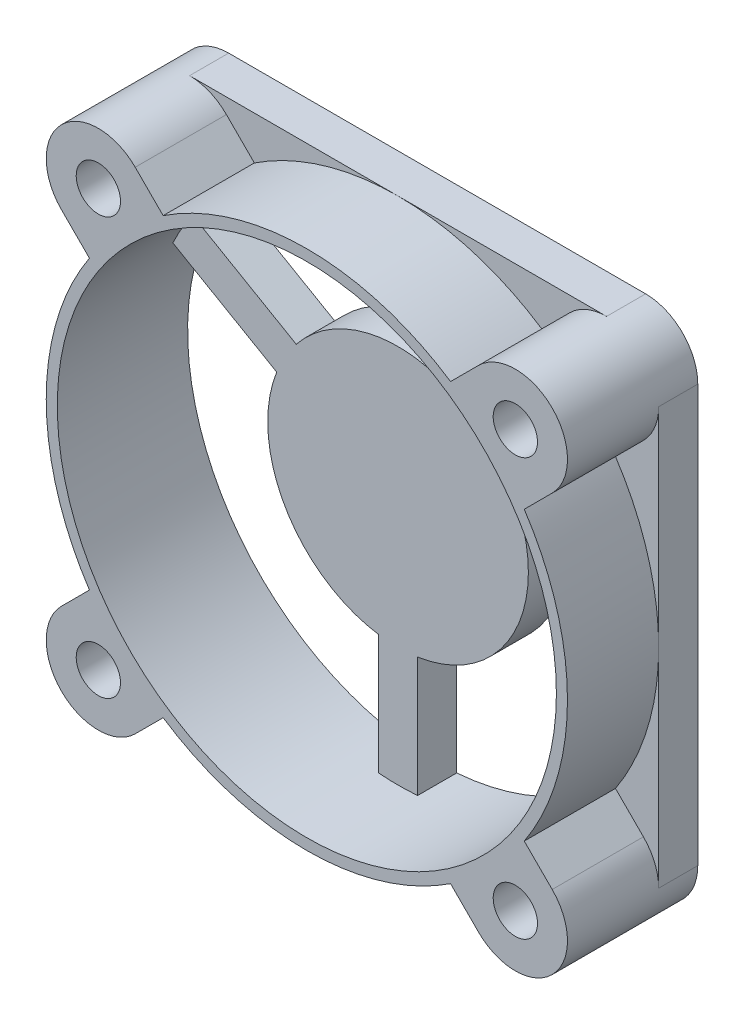
SolidWorks part; units mm, degrees
note: '?' marks a value the reader was unsure of.
material "PW100:Mi:0:30:C1:0:1:2:Re:16:"
ref_plane "Front" through (0, 0, 0) normal (0, 0, 1) x (1, 0, 0)
ref_plane "Top" through (0, 0, 0) normal (0, 1, 0) x (1, 0, 0)
ref_plane "Right" through (0, 0, 0) normal (1, 0, 0) x (0, 0, -1)
sketch "Support-Front" plane through (0, 0, 0) normal (0, 0, 1) x (1, 0, 0)
  line L0 (-20, 0) -> (20, 0) construction
  line L1 (0, 20) -> (0, -20) construction
  line L2 (20, -16) -> (20, 16)
  line L3 (-20, -16) -> (-20, 16)
  line L4 (16, 20) -> (-16, 20)
  line L5 (16, -20) -> (-16, -20)
  line L6 (0, 20) -> (0, 26.6274) construction
  arc A0 (20, 16) -> (16, 20) centre (16, 16) ccw
  arc A1 (-20, 16) -> (-16, 20) centre (-16, 16) cw
  arc A2 (-20, -16) -> (-16, -20) centre (-16, -16) ccw
  arc A3 (20, -16) -> (16, -20) centre (16, -16) cw
  circle A4 centre (16, 16) radius 1.7
  circle A5 centre (-16, 16) radius 1.7
  circle A6 centre (-16, -16) radius 1.7
  circle A7 centre (16, -16) radius 1.7
  circle A8 centre (0, 0) radius 19.15
  circle A9 centre (0, 0) radius 10
  circle A10 centre (0, 0) radius 20
  circle A11 centre (0, 0) radius 26.6274 construction
  dimension "Diam-Fixing-Hole" = 3.4
  dimension "Diam-Fan-Hole" = 38.3
  dimension "Diam-Fixing-Plate-Fan" = 20
  dimension "Width" = 40
  dimension "Dist-Fixing-Hole" = 32
sketch "Support-Right" plane through (0, 0, 0) normal (1, 0, 0) x (0, 0, -1)
  line L0 (-10, 0) -> (0, 0) construction
  line L1 (-5, 20) -> (-5, -20) construction
  line L2 (-3, 20) -> (-3, -20)
  line L3 (-10, 20) -> (0, 20)
  line L4 (-10, 20) -> (-10, -20)
  line L5 (-10, -20) -> (0, -20)
  line L6 (0, 20) -> (0, -20)
  line L7 (-7, 20) -> (-7, -20)
  dimension "Thickness" = 10
  dimension "Thickness-Flange" = 3
sketch "Support-Front-Reinforcment-Place" plane through (0, 0, 0) normal (0, 0, 1) x (1, 0, 0)
  line L0 (0, 20) -> (0, 0) construction
  line L2 (6.306, 20) -> (6.6671, 17.9519)
  line L3 (16, 20) -> (-16, 20) construction
  line L4 (-6.306, 20) -> (-6.6671, 17.9519)
  line L5 (6.306, 20) -> (0, 0) construction
  line L6 (-6.306, 20) -> (0, 0) construction
  line L7 (6.306, 20) -> (-6.306, 20)
  circle A3 centre (0, 0) radius 19.15 construction
  arc A4 (6.6671, 17.9519) -> (-6.6671, 17.9519) centre (0, 0) ccw
  dimension "D1" = 20
  dimension "D2" = 35
sketch "Support-Front-Reinforcment-Strip" plane through (0, 0, 0) normal (0, 0, 1) x (1, 0, 0)
  line L0 (11.028, 16.6848) -> (13.1716, 18.8284)
  line L1 (16.6848, 11.028) -> (18.8284, 13.1716)
  line L2 (16, 16) -> (0, 0) construction
  arc A0 (13.1716, 18.8284) -> (18.8284, 13.1716) centre (16, 16) cw
  arc A1 (20, 16) -> (16, 20) centre (16, 16) ccw construction
  circle A3 centre (0, 0) radius 20 construction
  arc A6 (16.6848, 11.028) -> (11.028, 16.6848) centre (0, 0) ccw
sketch "Support-Front-Bone" plane through (0, 0, 0) normal (0, 0, 1) x (1, 0, 0)
  line L0 (0, -10) -> (0, -19.15) construction
  line L1 (-1.5, -9.8869) -> (-1.5, -19.0912)
  line L2 (1.5, -9.8869) -> (1.5, -19.0912)
  line L3 (0, 0) -> (0, 20) construction
  line L4 (16, 20) -> (-16, 20) construction
  line L6 (0, 0) -> (0, -10) construction
  circle A0 centre (0, 0) radius 19.15 construction
  circle A1 centre (0, 0) radius 10 construction
  arc A2 (-1.5, -9.8869) -> (1.5, -9.8869) centre (0, 0) ccw
  arc A3 (-1.5, -19.0912) -> (1.5, -19.0912) centre (0, 0) ccw
  dimension "Angle-Bone" = 180
  dimension "Angle-Place-Bone" = 180
  dimension "Thickness-Flange" = 3
ref_plane "Plane1" through (0, 0, 10) normal (0, 0, 1) x (1, 0, 0)
sketch "Sketch-Body" plane through (0, 0, 0) normal (0, 0, 1) x (1, 0, 0)
  line L4 (-16, -20) -> (16, -20)
  line L5 (-20, 16) -> (-20, -16)
  line L6 (16, 20) -> (-16, 20)
  line L7 (20, -16) -> (20, 16)
  line L8 (-16, -20) -> (16, -20)
  line L9 (-20, 16) -> (-20, -16)
  line L10 (16, 20) -> (-16, 20)
  line L11 (20, -16) -> (20, 16)
  circle A0 centre (0, 0) radius 19.15 construction
  circle A1 centre (0, 0) radius 19.15
  arc A4 (-20, -16) -> (-16, -20) centre (-16, -16) ccw
  arc A5 (-16, 20) -> (-20, 16) centre (-16, 16) ccw
  arc A6 (20, 16) -> (16, 20) centre (16, 16) ccw
  arc A7 (16, -20) -> (20, -16) centre (16, -16) ccw
  arc A8 (-20, -16) -> (-16, -20) centre (-16, -16) ccw
  arc A9 (-16, 20) -> (-20, 16) centre (-16, 16) ccw
  arc A10 (20, 16) -> (16, 20) centre (16, 16) ccw
  arc A11 (16, -20) -> (20, -16) centre (16, -16) ccw
  dimension "D1" = 0
extrude "Body" add sketch "Sketch-Body" along normal up to surface (10 mm away) up to plane "Plane1"
sketch "Sketch-Cut-Body" plane through (0, 0, 0) normal (1, 0, 0) x (0, 0, -1)
  line L0 (-10, 0) -> (0, 0) construction
  line L1 (-10, 0) -> (0, 0) construction
  line L2 (-10, 19.15) -> (-10, -19.15) construction
  line L4 (-10, 20) -> (0, 20) construction
  line L5 (-10, 20) -> (-10, 26.6274)
  line L6 (-10, 26.6274) -> (-3, 26.6274)
  line L7 (-10, 20) -> (-3, 20)
  line L9 (-3, 26.6274) -> (-3, 20)
  line L10 (-3, 20) -> (-3, -20) construction
revolve "Cut-Body" cut sketch "Sketch-Cut-Body" angle 360 about L1
sketch "Sketch-Reinforcment-Place" plane through (0, 0, 0) normal (0, 0, 1) x (1, 0, 0)
  line L0 (16, 20) -> (-16, 20) construction
  line L1 (6.306, 20) -> (6.6671, 17.9519) construction
  line L2 (-6.306, 20) -> (-6.6671, 17.9519) construction
  line L3 (6.306, 20) -> (-6.306, 20)
  line L4 (6.306, 20) -> (6.6671, 17.9519)
  line L5 (-6.306, 20) -> (-6.6671, 17.9519)
  circle A0 centre (0, 0) radius 19.15 construction
  arc A1 (6.6671, 17.9519) -> (-6.6671, 17.9519) centre (0, 0) ccw
extrude "Reinforcment-Place" [suppressed] add sketch "Sketch-Reinforcment-Place" along normal up to surface (25.5 mm away)
pattern_circular "CirPattern-Reinforcment-Place" [suppressed] count 1 over? 360?
sketch "Sketch-Reinforcment-Strip" plane through (0, 0, 0) normal (0, 0, 1) x (1, 0, 0)
  line L0 (16.6848, 11.028) -> (18.8284, 13.1716) construction
  line L1 (11.028, 16.6848) -> (13.1716, 18.8284) construction
  line L2 (16.6848, 11.028) -> (18.8284, 13.1716)
  line L3 (11.028, 16.6848) -> (13.1716, 18.8284)
  arc A0 (18.8284, 13.1716) -> (13.1716, 18.8284) centre (16, 16) ccw construction
  circle A1 centre (0, 0) radius 20 construction
  arc A2 (18.8284, 13.1716) -> (13.1716, 18.8284) centre (16, 16) ccw
  arc A3 (16.6848, 11.028) -> (11.028, 16.6848) centre (0, 0) ccw
extrude "Reinforcment-Strip" add sketch "Sketch-Reinforcment-Strip" along normal up to surface (10 mm away) up to plane "Plane1"
pattern_circular "CirPattern-Reinforcment-Strip" count 4 over 360 about axis through (0, 0, 0) along (0, 0, 1) of "Reinforcment-Strip"
sketch "Sketch-Fixing-Hole" plane through (0, 0, 0) normal (0, 0, 1) x (1, 0, 0)
  circle A0 centre (16, 16) radius 1.7 construction
  circle A1 centre (16, 16) radius 1.7
extrude "Fixing-Hole" cut sketch "Sketch-Fixing-Hole" along normal through all
pattern_circular "CirPattern-Fixing-Hole" count 4 over 360 about axis through (0, 0, 0) along (0, 0, 1) of "Fixing-Hole"
sketch "Sketch-Bone" plane through (0, 0, 0) normal (0, 0, 1) x (1, 0, 0)
  line L0 (1.5, -9.8869) -> (1.5, -19.0912) construction
  line L1 (-1.5, -9.8869) -> (-1.5, -19.0912) construction
  line L2 (1.5, -9.8869) -> (1.5, -19.0912)
  line L3 (-1.5, -9.8869) -> (-1.5, -19.0912)
  circle A0 centre (0, 0) radius 19.15 construction
  circle A1 centre (0, 0) radius 10 construction
  arc A2 (-1.5, -19.0912) -> (1.5, -19.0912) centre (0, 0) ccw
  arc A3 (-1.5, -9.8869) -> (1.5, -9.8869) centre (0, 0) ccw
extrude "Bone" add sketch "Sketch-Bone" along normal blind 3
pattern_circular "CirPattern-Bone" count 3 over 360 about axis through (0, 0, 0) along (0, 0, 1) of "Bone"
sketch "Sketch-Fixing-Plate-Fan" plane through (0, 0, 0) normal (0, 0, 1) x (1, 0, 0)
  circle A0 centre (0, 0) radius 10 construction
  circle A1 centre (0, 0) radius 10
extrude "Fixing-Plate-Fan" add sketch "Sketch-Fixing-Plate-Fan" along normal blind 3
